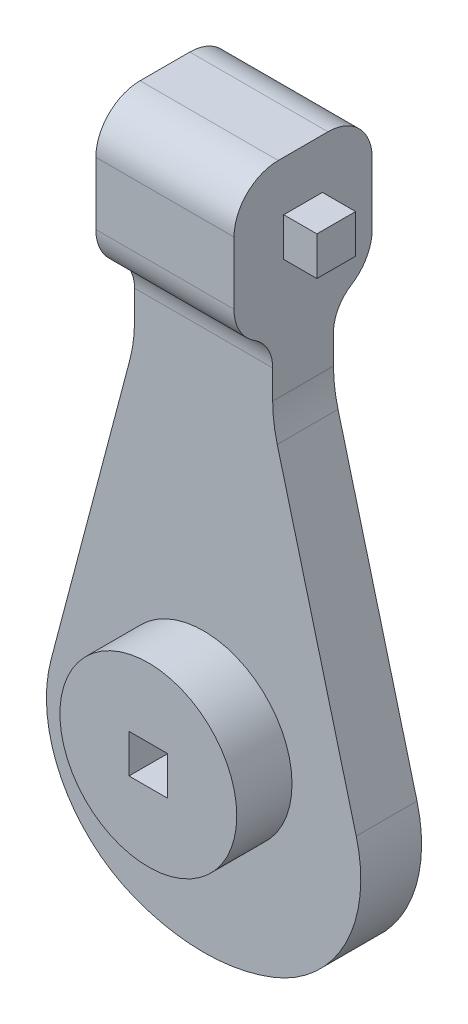
SolidWorks part; units mm, degrees
ref_plane "Front Plane" through (0, 0, 0) normal (0, 0, 1) x (1, 0, 0)
ref_plane "Top Plane" through (0, 0, 0) normal (0, 1, 0) x (1, 0, 0)
ref_plane "Right Plane" through (0, 0, 0) normal (1, 0, 0) x (0, 0, -1)
sketch "Sketch1" plane through (0, 0, 0) normal (0, 0, 1) x (1, 0, 0)
  line L0 (0, 0) -> (0, 55) construction
  line L1 (-12.5, 55) -> (12.5, 55)
  line L2 (-27.6176, -2.366) -> (-13.3253, 51.8681)
  line L3 (-12.5, 58.2388) -> (-12.5, 67.3073)
  line L4 (27.6176, -2.366) -> (13.3253, 51.8681)
  line L5 (12.5, 58.2388) -> (12.5, 67.3073)
  line L6 (-12.5, 67.3073) -> (-12.5, 95.9037)
  line L7 (12.5, 67.3073) -> (12.5, 95.9037)
  circle A0 centre (0, 0) radius 20
  arc A1 (12.6088, -31.9959) -> (-12.6088, -31.9959) centre (0, 0) cw
  arc A2 (-12.5, 95.9037) -> (12.5, 95.9037) centre (0, 82.9518) cw
  arc A3 (-27.6176, -2.366) -> (-12.6088, -31.9959) centre (-3.4429, -8.7367) ccw
  arc A4 (27.6176, -2.366) -> (12.6088, -31.9959) centre (3.4429, -8.7367) cw
  arc A5 (-12.5, 58.2388) -> (-13.3253, 51.8681) centre (-37.5, 58.2388) cw
  arc A6 (12.5, 58.2388) -> (13.3253, 51.8681) centre (37.5, 58.2388) ccw
  arc A7 (-14.04, 71.6878) -> (-12.5, 67.3073) centre (-19.5, 67.3073) cw
  arc A8 (14.04, 71.6878) -> (12.5, 67.3073) centre (19.5, 67.3073) ccw
  circle A9 centre (0, 82.9518) radius 4
  point P9 (0, 55)
  point P14 (-30.947, -15)
  point P17 (30.947, -15)
  point P26 (-12.5, 70)
  point P29 (12.5, 70)
  dimension "D1" = 40
  dimension "D5" = 18
  dimension "D6" = 25
  dimension "D7" = 25
  dimension "D8" = 25
  dimension "D9" = 25
  dimension "D10" = 7
  dimension "D11" = 7
  dimension "D12" = 8
  dimension "D2" = 55
  dimension "D3" = 15
  dimension "D4" = 25
extrude "Boss-Extrude1" add sketch "Sketch1" against normal blind 11 contours A8 A2 A7 L3 A5 L2 A3 A1 A4 L4 A6 L5 A9 A0 region at (0, 30.0502, 0)
extrude "Boss-Extrude2" add sketch "Sketch1<4>" against normal blind 6 contours A0 region at (0, 0, 0)
sketch "Sketch1<4>" plane through (0, 0, 0) normal (0, 0, 1) x (1, 0, 0) same geometry as "Sketch1"
sketch "Sketch3" plane through (0, 0, 0) normal (0, 0, 1) x (1, 0, 0)
  circle A0 centre (0, 0) radius 16
  dimension "D1" = 32
extrude "Boss-Extrude3" add sketch "Sketch3" along normal blind 10
sketch "Sketch4" plane through (0, 0, 10) normal (0, 0, 1) x (1, 0, 0)
  line L0 (-3.5, -3.5) -> (-3.5, 3.5)
  line L1 (-3.5, -3.5) -> (3.5, -3.5)
  line L2 (-3.5, 3.5) -> (3.5, 3.5)
  line L3 (3.5, -3.5) -> (3.5, 3.5)
  line L4 (-3.5, -3.5) -> (3.5, 3.5) construction
  line L5 (-3.5, 3.5) -> (3.5, -3.5) construction
  point P1 (0, 0)
  dimension "D1" = 7
  dimension "D2" = 7
extrude "Cut-Extrude1" cut sketch "Sketch4" against normal blind 7
sketch "Sketch5" plane through (0, 0, 0) normal (0, 0, 1) x (1, 0, 0)
  line L1 (-12.5, 70.4518) -> (12.5, 70.4518)
  line L2 (-12.5, 70.4518) -> (-12.5, 95.4518)
  line L3 (-12.5, 95.4518) -> (12.5, 95.4518)
  line L4 (12.5, 70.4518) -> (12.5, 95.4518)
  line L5 (-12.5, 70.4518) -> (12.5, 95.4518) construction
  line L6 (-12.5, 95.4518) -> (12.5, 70.4518) construction
  point P0 (0, 82.9518)
  dimension "D1" = 25
  dimension "D2" = 25
extrude "Boss-Extrude4" add sketch "Sketch5" along normal blind 7 and the other way blind 18
sketch "Sketch6" plane through (12.5, 0, 0) normal (1, 0, 0) x (0, 0, -1)
  line L0 (18, 95.4518) -> (18, 70.4518) construction
  line L1 (18, 82.9518) -> (-7, 82.9518) construction
  line L2 (-7, 70.4518) -> (-7, 95.4518) construction
  line L4 (2, 79.4518) -> (9, 79.4518)
  line L5 (2, 79.4518) -> (2, 86.4518)
  line L6 (2, 86.4518) -> (9, 86.4518)
  line L7 (9, 79.4518) -> (9, 86.4518)
  line L8 (2, 79.4518) -> (9, 86.4518) construction
  line L9 (2, 86.4518) -> (9, 79.4518) construction
  point P8 (5.5, 82.9518)
  dimension "D1" = 7
  dimension "D2" = 7
extrude "Boss-Extrude5" add sketch "Sketch6" along normal blind 6
mirror "Mirror1" about plane through (0, 0, 0) normal (1, 0, 0) of "Boss-Extrude5"
sketch "Sketch7" plane through (0, 0, 0) normal (0, 0, 1) x (1, 0, 0)
  line L3 (-12.5, 95.4518) -> (12.5, 95.4518)
  line L4 (12.5, 95.4518) -> (12.5, 95.9037)
  line L5 (-12.5, 95.9037) -> (-12.5, 95.4518)
  line L6 (-12.5, 95.4518) -> (12.5, 95.4518)
  line L7 (12.5, 95.4518) -> (12.5, 95.9037)
  line L8 (-12.5, 95.9037) -> (-12.5, 95.4518)
  arc A1 (12.5, 95.9037) -> (-12.5, 95.9037) centre (0, 82.9518) ccw
  arc A2 (12.5, 95.9037) -> (-12.5, 95.9037) centre (0, 82.9518) ccw
  dimension "D1" = 0
extrude "Cut-Extrude2" cut sketch "Sketch7" against normal up to surface (11 mm away) up to face at (0, 96.9398, -11)
fillet "Fillet1" radius 7 1 edges at (0, 70.4518, 0) type face fillet first side face at (0, 70.4518, 3.5) second side face at (0, 28.424, 0)
fillet "Fillet2" radius 7 1 edges at (0, 70.4518, -11) type face fillet first side face at (0, 70.4518, -14.5) second side face at (20, 0, -11)
fillet "Fillet3" radius 8 4 edges at (0, 70.4518, 7) (0, 70.4518, -18) (0, 95.4518, -18) (0, 95.4518, 7)
